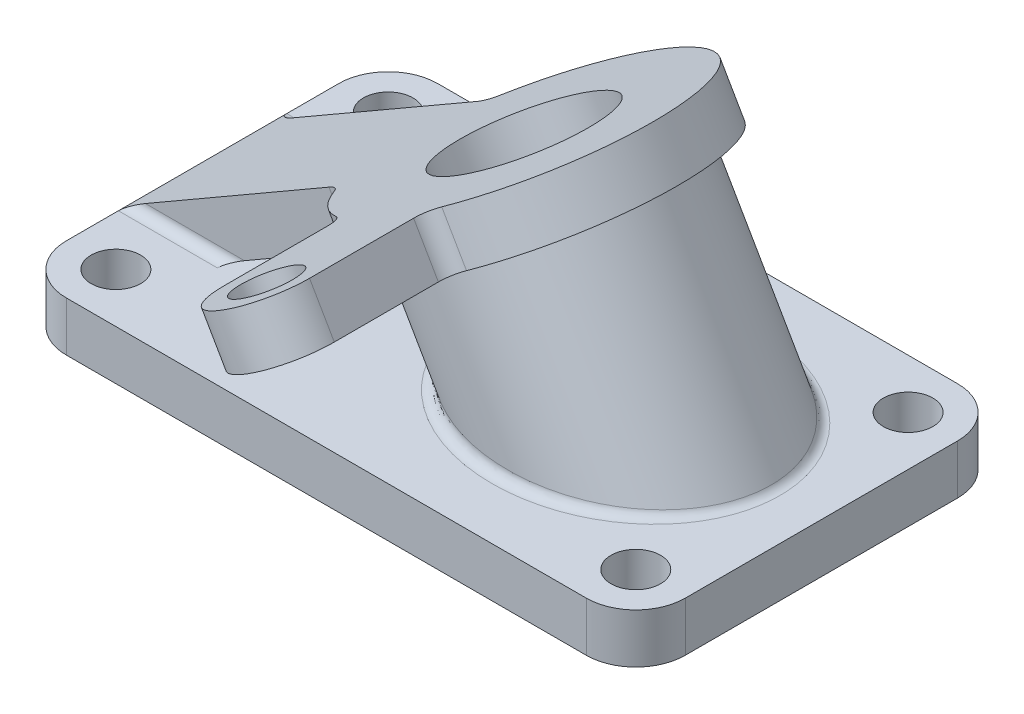
SolidWorks part; units mm, degrees
ref_plane "前视基准面" through (0, 0, 0) normal (0, 0, 1) x (1, 0, 0)
ref_plane "上视基准面" through (0, 0, 0) normal (0, 1, 0) x (1, 0, 0)
ref_plane "右视基准面" through (0, 0, 0) normal (1, 0, 0) x (0, 0, -1)
sketch "草图1" plane through (0, 0, 0) normal (0, 1, 0) x (1, 0, 0)
  line L0 (-62.5, 37.5) -> (62.5, -37.5) construction
  line L1 (-52.5, 37.5) -> (52.5, 37.5)
  line L2 (-62.5, 27.5) -> (-62.5, -27.5)
  line L3 (-52.5, -37.5) -> (52.5, -37.5)
  line L4 (62.5, 27.5) -> (62.5, -27.5)
  arc A0 (-62.5, -27.5) -> (-52.5, -37.5) centre (-52.5, -27.5) ccw
  arc A1 (52.5, -37.5) -> (62.5, -27.5) centre (52.5, -27.5) ccw
  arc A2 (52.5, 37.5) -> (62.5, 27.5) centre (52.5, 27.5) cw
  arc A3 (-52.5, 37.5) -> (-62.5, 27.5) centre (-52.5, 27.5) ccw
  circle A4 centre (-52.5, -27.5) radius 5
  circle A5 centre (52.5, -27.5) radius 5
  circle A6 centre (52.5, 27.5) radius 5
  circle A7 centre (-52.5, 27.5) radius 5
  point P7 (-62.5, -37.5)
  point P13 (62.5, 37.5)
  dimension "D3" = 10
  dimension "D4" = 10
  dimension "D5" = 10
  dimension "D6" = 10
  dimension "D7" = 10
  dimension "D1" = 125
  dimension "D2" = 75
extrude "凸台-拉伸1" add sketch "草图1" along normal blind 10
ref_plane "基准面4" through (-19.9551, 34.5633, 0) normal (-0.5, 0.866, 0) x (0, 0, 1)
sketch "草图4" plane through (-19.9551, 34.5633, 0) normal (-0.5, 0.866, 0) x (0, 0, 1)
  line L0 (0, 47.52) -> (0, -49.1266) construction
  line L1 (-27.5, -49.1266) -> (27.5, -49.1266) construction
  line L2 (-69.0609, 25.8734) -> (69.0609, 25.8734) construction
  line L3 (30.9839, 35.8734) -> (52, 35.8734)
  line L4 (30.9839, 15.8734) -> (52, 15.8734)
  line L5 (-15, -2.3223) -> (-15, -49.1266)
  line L6 (15, -2.3223) -> (15, -49.1266)
  line L7 (-39.255, -49.1266) -> (39.255, -49.1266) construction
  line L8 (-15, -49.1266) -> (15, -49.1266)
  arc A0 (27.3387, 38.2264) -> (-16.7647, 0.9948) centre (0, 25.8734) ccw
  circle A1 centre (0, 25.8734) radius 15
  arc A2 (52, 15.8734) -> (52, 35.8734) centre (52, 25.8734) ccw
  arc A3 (27.3387, 38.2264) -> (30.9839, 35.8734) centre (30.9839, 39.8734) ccw
  arc A4 (30.9839, 15.8734) -> (27.3387, 13.5205) centre (30.9839, 11.8734) ccw
  arc A5 (16.7647, 0.9948) -> (15, -2.3223) centre (19, -2.3223) ccw
  arc A6 (-15, -2.3223) -> (-16.7647, 0.9948) centre (-19, -2.3223) ccw
  arc A7 (16.7647, 0.9948) -> (27.3387, 13.5205) centre (0, 25.8734) ccw
  circle A8 centre (52, 25.8734) radius 6
  dimension "D1" = 30
  dimension "D3" = 15
  dimension "D4" = 20
  dimension "D6" = 8
  dimension "D7" = 8
  dimension "D9" = 8
  dimension "D10" = 8
  dimension "D11" = 6
  dimension "D2" = 75
  dimension "D5" = 52
  dimension "D8" = 30
sketch "草图5" plane through (0, 0, 0) normal (0, -1, 0) x (1, 0, 0)
  line L0 (40.5, 27.5) -> (-40.5, 27.5)
  line L1 (-52.5, 15.5) -> (-52.5, -15.5)
  line L2 (-40.5, -27.5) -> (40.5, -27.5)
  line L3 (52.5, -15.5) -> (52.5, 15.5)
  arc A0 (-52.5, 15.5) -> (-40.5, 27.5) centre (-52.5, 27.5) ccw
  arc A1 (40.5, 27.5) -> (52.5, 15.5) centre (52.5, 27.5) ccw
  arc A2 (52.5, -15.5) -> (40.5, -27.5) centre (52.5, -27.5) ccw
  arc A3 (-40.5, -27.5) -> (-52.5, -15.5) centre (-52.5, -27.5) ccw
  dimension "D1" = 24
  dimension "D2" = 24
  dimension "D3" = 24
  dimension "D4" = 24
extrude "切除-拉伸1" cut sketch "草图5" against normal blind 4
extrude "凸台-拉伸2" add sketch "草图4" against normal blind 10
sketch "草图6" plane through (-14.9551, 25.903, 0) normal (0.5, -0.866, 0) x (0.866, 0.5, 0)
  circle A0 centre (25.8734, 0) radius 25
  circle A1 centre (25.8734, 0) radius 15 construction
  point P4 (0, 0)
  dimension "D1" = 50
extrude "凸台-拉伸7" add sketch "草图6" along normal up to next
sketch "草图13" plane through (-19.9551, 34.5633, 0) normal (-0.5, 0.866, 0) x (0, 0, 1)
  circle A0 centre (0, 25.8734) radius 15
  circle A1 centre (0, 25.8734) radius 15 construction
extrude "切除-拉伸2" cut sketch "草图13" against normal through all
fillet "圆角7" radius 2 1 edges at (-52.5, 10, 15)
fillet "圆角8" radius 2 1 edges at (-52.5, 10, -15)
fillet "圆角9" radius 2 1 edges at (-4.765, 10, 0)
fillet "圆角10" radius 1 1 edges at (-14.1987, 26.3397, 0)
